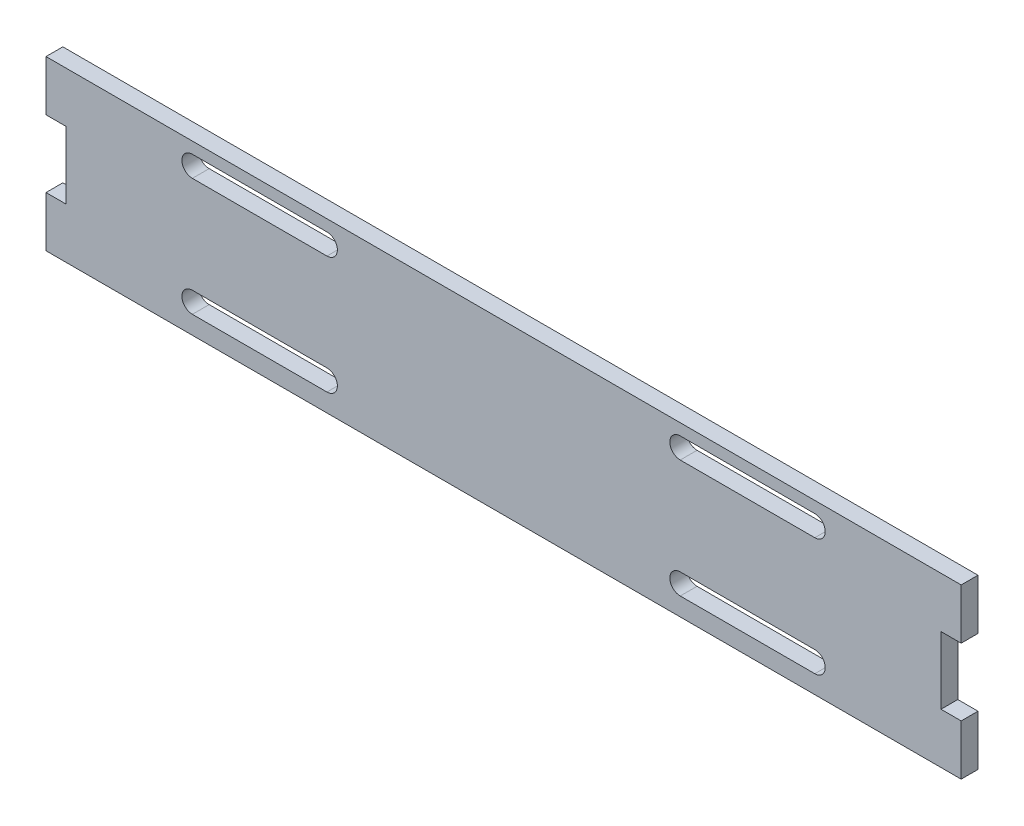
SolidWorks part; units mm, degrees
ref_plane "前基準面" through (0, 0, 0) normal (0, 0, 1) x (1, 0, 0)
ref_plane "上基準面" through (0, 0, 0) normal (0, 1, 0) x (1, 0, 0)
ref_plane "右基準面" through (0, 0, 0) normal (1, 0, 0) x (0, 0, -1)
sketch "草圖1" plane through (0, 0, 0) normal (0, 0, 1) x (1, 0, 0)
  line L0 (136, -25) -> (136, -10)
  line L1 (136, 25) -> (-136, 25)
  line L2 (130, 10) -> (130, -10)
  line L3 (136, -25) -> (-136, -25)
  line L4 (-130, 10) -> (-130, -10)
  line L5 (0, -25) -> (0, 25) construction
  line L6 (130, 0) -> (-130, 0) construction
  line L9 (-130, 10) -> (-136, 10)
  line L10 (-136, 25) -> (-136, 10)
  line L13 (-130, -10) -> (-136, -10)
  line L14 (-136, -25) -> (-136, -10)
  line L15 (130, -10) -> (136, -10)
  line L16 (130, 10) -> (136, 10)
  line L17 (136, 25) -> (136, 10)
  point P0 (0, 0)
  point P1 (0, 0)
  point P2 (0, 0)
  point P3 (0, 0)
  point P8 (0, 0)
  point P13 (-136, -17.5)
  point P14 (136, -17.5)
  dimension "D1" = 260
  dimension "D2" = 6
  dimension "D3" = 15
  dimension "D4" = 6
  dimension "D5" = 50
extrude "填料-伸長1" add sketch "草圖1" along normal blind 5
sketch "草圖2" plane through (0, 0, 5) normal (0, 0, 1) x (1, 0, 0)
  line L0 (-92.5, 18.5) -> (-52.5, 18.5) construction
  line L1 (-92.5, 21.6) -> (-52.5, 21.6)
  line L2 (-92.5, 15.4) -> (-52.5, 15.4)
  line L3 (-92.5, -16.5) -> (-52.5, -16.5) construction
  line L4 (-92.5, -13.4) -> (-52.5, -13.4)
  line L5 (-92.5, -19.6) -> (-52.5, -19.6)
  line L6 (0, 61.8937) -> (0, -44.053) construction
  line L7 (-136, -25) -> (136, -25) construction
  line L8 (52.5, 18.5) -> (92.5, 18.5) construction
  line L9 (52.5, 21.6) -> (92.5, 21.6)
  line L10 (52.5, 15.4) -> (92.5, 15.4)
  line L11 (52.5, -16.5) -> (92.5, -16.5) construction
  line L12 (52.5, -13.4) -> (92.5, -13.4)
  line L13 (52.5, -19.6) -> (92.5, -19.6)
  arc A0 (-92.5, 21.6) -> (-92.5, 15.4) centre (-92.5, 18.5) ccw
  arc A1 (-52.5, 15.4) -> (-52.5, 21.6) centre (-52.5, 18.5) ccw
  arc A2 (-92.5, -13.4) -> (-92.5, -19.6) centre (-92.5, -16.5) ccw
  arc A3 (-52.5, -19.6) -> (-52.5, -13.4) centre (-52.5, -16.5) ccw
  arc A4 (52.5, 21.6) -> (52.5, 15.4) centre (52.5, 18.5) ccw
  arc A5 (92.5, 15.4) -> (92.5, 21.6) centre (92.5, 18.5) ccw
  arc A6 (52.5, -13.4) -> (52.5, -19.6) centre (52.5, -16.5) ccw
  arc A7 (92.5, -19.6) -> (92.5, -13.4) centre (92.5, -16.5) ccw
  point P2 (-72.5, 18.5)
  point P7 (-72.5, -16.5)
  point P21 (0, 0)
  point P22 (72.5, 18.5)
  point P27 (72.5, -16.5)
  point P34 (70.7086, -16.5)
  point P35 (0, 0)
  point P36 (-52.9586, 18.5)
  point P37 (-95.6, -16.5)
  point P38 (49.4, -16.5)
  dimension "D3" = 3.1
  dimension "D1" = 35
  dimension "D2" = 5.4
  dimension "D4" = 40
  dimension "D6" = 145
  dimension "D5" = 2
extrude "除料-伸長1" cut sketch "草圖2" against normal through all
